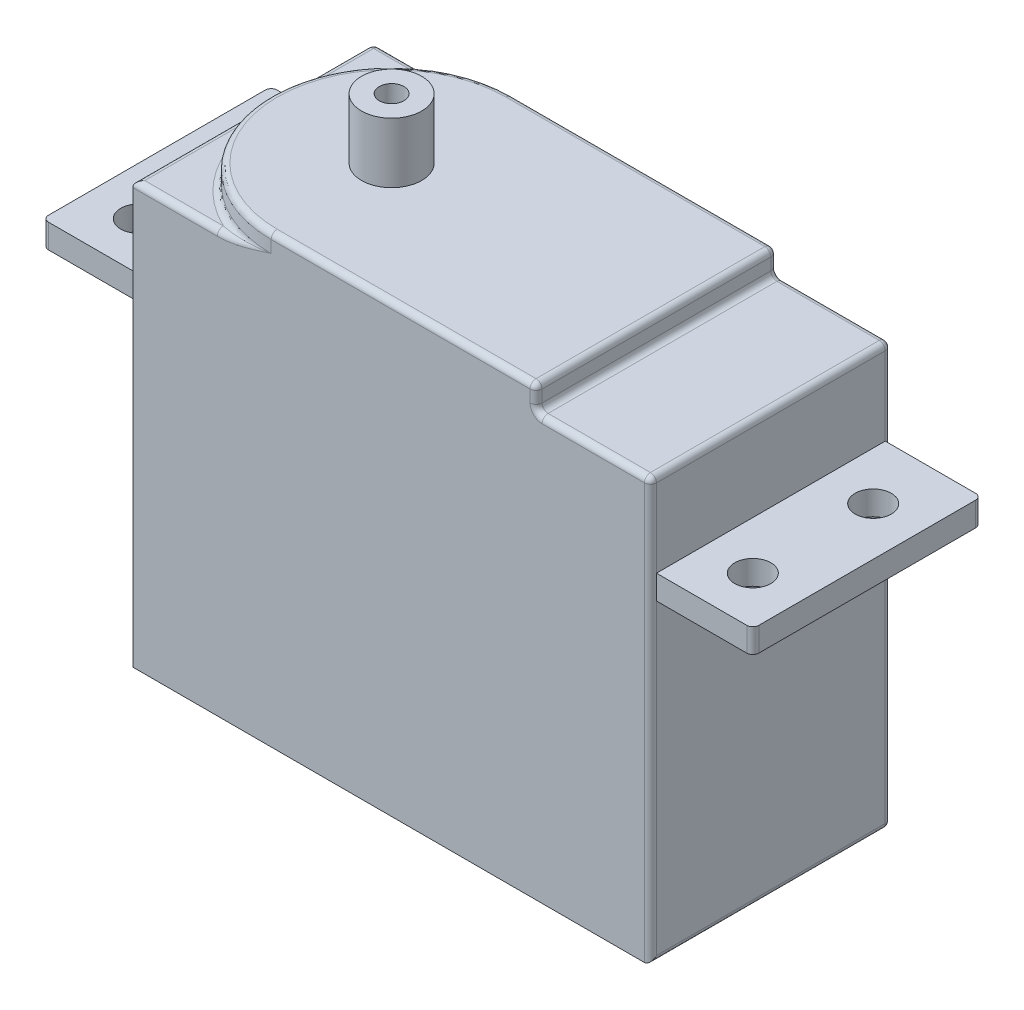
SolidWorks part; units mm, degrees
ref_plane "Front Plane" through (0, 0, 0) normal (0, 0, 1) x (1, 0, 0)
ref_plane "Top Plane" through (0, 0, 0) normal (0, 1, 0) x (1, 0, 0)
ref_plane "Right Plane" through (0, 0, 0) normal (1, 0, 0) x (0, 0, -1)
sketch "Sketch1" plane through (0, 0, 0) normal (0, 1, 0) x (1, 0, 0)
  line L1 (-21.5, 10) -> (21.5, 10)
  line L2 (-21.5, 10) -> (-21.5, -10)
  line L3 (-21.5, -10) -> (21.5, -10)
  line L4 (21.5, 10) -> (21.5, -10)
  line L5 (-21.5, 10) -> (21.5, -10) construction
  line L6 (-21.5, -10) -> (21.5, 10) construction
  point P0 (0, 0)
  dimension "D1" = 43
  dimension "D2" = 20
extrude "Boss-Extrude1" add sketch "Sketch1" along normal blind 35
sketch "Sketch2" plane through (0, 35, 0) normal (0, 1, 0) x (1, 0, 0)
  line L0 (-21.5, -10) -> (21.5, -10) construction
  line L1 (-10, 10) -> (12, 10)
  line L3 (-10, -10) -> (12, -10)
  line L4 (12, 10) -> (12, -10)
  arc A0 (-10, 10) -> (-10, -10) centre (-10, 0) ccw
extrude "Boss-Extrude2" add sketch "Sketch2" along normal blind 2
fillet "Fillet1" radius 0.5 19 edges at (-20, 35, 0) (12, 35, 0) (-20, 37, 0) (1, 37, 10) (12, 37, 0) (1, 37, -10) (12, 36, -10) (12, 36, 10) (21.5, 0, 0) (0, 0, -10) (21.5, 35, 0) (-15.75, 35, -10) (16.75, 35, -10) (-21.5, 35, 0) (16.75, 35, 10) (-15.75, 35, 10) (21.5, 17.5, 10) (-21.5, 17.5, -10) (21.5, 17.5, -10)
sketch "Sketch3" plane through (21.5, 0, 0) normal (1, 0, 0) x (0, 0, -1)
  line L0 (-9.5, 34.5) -> (-9.5, 0.5) construction
  line L1 (-9.5, 28.0058) -> (9.5, 28.0058)
  line L2 (-9.5, 28.0058) -> (-9.5, 26.0058)
  line L3 (-9.5, 26.0058) -> (9.5, 26.0058)
  line L4 (9.5, 28.0058) -> (9.5, 26.0058)
  line L5 (9.5, 0.5) -> (9.5, 34.5) construction
  dimension "D1" = 2
extrude "Boss-Extrude3" add sketch "Sketch3" along normal blind 8
fillet "Fillet3" radius 0.5 2 edges at (29.5, 27.0058, 9.5) (29.5, 27.0058, -9.5)
hole_wizard "Ø3.0mm Dowel Hole1" positions "Sketch6" profile "Sketch7" hole size "Ø3.0" standard "ISO"
sketch "Sketch6" plane through (0, 28.0058, 0) normal (0, 1, 0) x (1, 0, 0)
  line L0 (29.5, 9) -> (29.5, -9) construction
  point P0 (25.5, -5.4982)
  point P2 (25.5, 4.5018)
  dimension "D1" = 4
  dimension "D2" = 10
sketch "Sketch7" plane through (25.5, 28.0058, 5.4982) normal (1, 0, 0) x (0, 0, 1)
  line L0 (0, 0) -> (0, 3.9013)
  line L1 (0, 3.9013) -> (1.5, 3)
  line L2 (1.5, 3) -> (1.5, 0)
  line L5 (1.5, 0) -> (0, 0)
  line L10 (0, 3.9013) -> (-1.5, 3) construction
  line L11 (0, -6.35) -> (0, 107.95) construction
  dimension "Hole Dia." = 3
  dimension "Hole Depth" = 3
  dimension "Drill Angle" = 118
mirror "Mirror4" about plane through (0, 0, 0) normal (1, 0, 0) of "Boss-Extrude3", "Fillet3", "Ø3.0mm Dowel Hole1"
sketch "Sketch8" plane through (0, 37, 0) normal (0, 1, 0) x (1, 0, 0)
  circle A0 centre (-10, 0) radius 2.5
  dimension "D1" = 5
extrude "Boss-Extrude4" add sketch "Sketch8" along normal blind 5
hole_wizard "M2.5 Tapped Hole1" positions "Sketch12" profile "Sketch13" tap size "M2.5" standard "ISO"
sketch "Sketch12" plane through (0, 42, 0) normal (0, 1, 0) x (1, 0, 0)
  point P0 (-10, 0)
sketch "Sketch13" plane through (-10, 42, 0) normal (1, 0, 0) x (0, 0, 1)
  line L0 (0, 0) -> (0, 3.6159)
  line L1 (0, 3.6159) -> (1.025, 3)
  line L2 (1.025, 3) -> (1.025, 0)
  line L5 (1.025, 0) -> (0, 0)
  line L10 (0, 3.6159) -> (-1.025, 3) construction
  line L11 (0, -6.35) -> (0, 107.95) construction
  dimension "Tap Drill Dia." = 2.05
  dimension "Tap Drill Depth" = 3
  dimension "Drill Angle" = 118
cosmetic thread "Hole Thread1" parameters "D1"=3, "D2"=2.5
